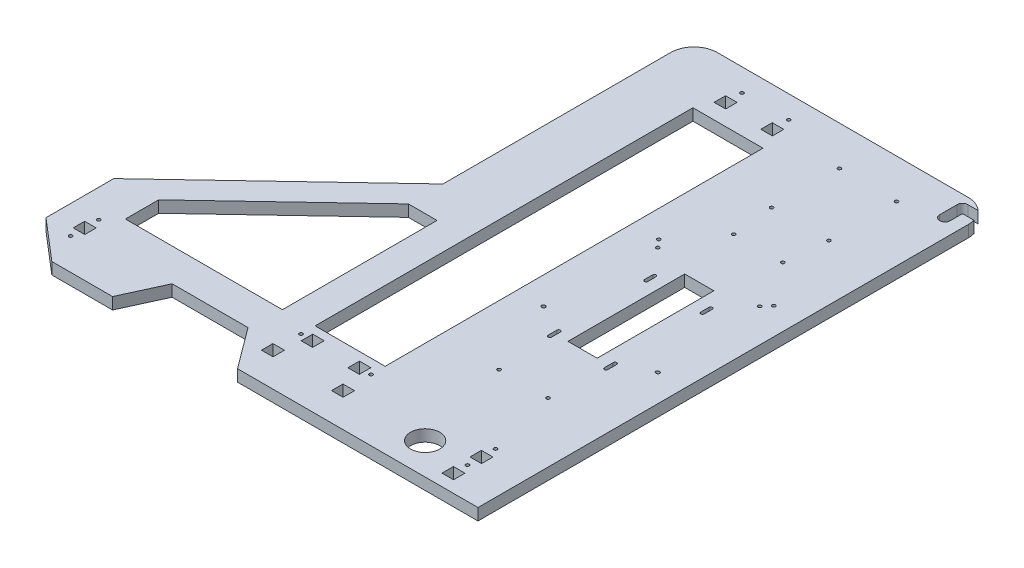
SolidWorks part; units mm, degrees
ref_plane "Front Plane" through (0, 0, 0) normal (0, 0, 1) x (1, 0, 0)
ref_plane "Top Plane" through (0, 0, 0) normal (0, 1, 0) x (1, 0, 0)
ref_plane "Right Plane" through (0, 0, 0) normal (1, 0, 0) x (0, 0, -1)
sketch "Sketch1" plane through (0, 0, 0) normal (0, 1, 0) x (1, 0, 0)
  line L0 (0, 0) -> (-235, 0)
  line L1 (-235, 0) -> (-235, -215)
  line L2 (-235, -215) -> (-380, -352)
  line L3 (-380, -352) -> (-380, -410)
  line L4 (-380, -410) -> (-345, -440)
  line L5 (-345, -440) -> (-293, -440)
  line L6 (-293, -440) -> (-277, -405)
  line L7 (-277, -405) -> (-212, -405)
  line L8 (-212, -405) -> (-185.9255, -440)
  line L9 (-185.9255, -440) -> (0, -440)
  line L10 (0, 0) -> (0, -440)
  line L12 (-293, -440) -> (-185.9255, -440) construction
  dimension "D3" = 235
  dimension "D5" = 58
  dimension "D13" = 190
  dimension "D7" = 35
  dimension "D2" = 126.686
  dimension "D11" = 65
  dimension "D15" = 52
  dimension "D12" = 30
  dimension "D10" = 35
  dimension "D14" = 16
  dimension "D6" = 380
  dimension "D4" = 440
extrude "Boss-Extrude1" add sketch "Sketch1" along normal blind 10
sketch "Sketch16" plane through (0, 10, 0) normal (0, 1, 0) x (1, 0, 0)
  line L0 (0, -440) -> (20, -440)
  line L1 (20, -440) -> (20, 0)
  line L2 (20, 0) -> (0, 0)
  line L3 (0, 0) -> (0, -440)
  dimension "D1" = 20
  dimension "D2" = 90
extrude "Boss-Extrude2" add sketch "Sketch16" against normal through all
sketch "Sketch2" plane through (0, 10, 0) normal (0, 1, 0) x (1, 0, 0)
  line L0 (-235, -215) -> (-235, -405) construction
  line L1 (-277, -405) -> (-212, -405) construction
  line L2 (-345, -440) -> (-345, -318.931) construction
  line L3 (-235, -215) -> (-380, -352) construction
  line L4 (-345, -348.5097) -> (-235, -244.5787)
  line L5 (-235, -244.5787) -> (-210.5, -244.5787)
  line L6 (-210.5, -244.5787) -> (-210.5, -377)
  line L7 (-210.5, -377) -> (-345, -377)
  line L8 (-345, -377) -> (-345, -348.5097)
  line L9 (0, -440) -> (0, 0) construction
  line L10 (-184.5, -375) -> (-124.5, -375)
  line L11 (-184.5, -375) -> (-184.5, -51.4)
  line L12 (-184.5, -51.4) -> (-124.5, -51.4)
  line L13 (-124.5, -375) -> (-124.5, -51.4)
  line L14 (-124.5, -387.1) -> (-184.5, -387.1) construction
  line L15 (-16, -440) -> (-16, 0) construction
  line L16 (20, 0) -> (-235, 0) construction
  line L17 (-355.85, -430.7) -> (-355.85, -329.1824) construction
  line L18 (-20.95, -429.9) -> (-11.05, -429.9)
  line L19 (-20.95, -429.9) -> (-20.95, -420.1)
  line L20 (-20.95, -420.1) -> (-11.05, -420.1)
  line L21 (-11.05, -429.9) -> (-11.05, -420.1)
  line L22 (-20.95, -429.9) -> (-11.05, -420.1) construction
  line L23 (-20.95, -420.1) -> (-11.05, -429.9) construction
  line L24 (-20.95, -405.9) -> (-11.05, -405.9)
  line L25 (-20.95, -405.9) -> (-20.95, -396.1)
  line L26 (-20.95, -396.1) -> (-11.05, -396.1)
  line L27 (-11.05, -405.9) -> (-11.05, -396.1)
  line L28 (-20.95, -405.9) -> (-11.05, -396.1) construction
  line L29 (-20.95, -396.1) -> (-11.05, -405.9) construction
  line L30 (-380, -410) -> (-345, -440) construction
  line L32 (-350.9, -396.1) -> (-360.8, -396.1)
  line L33 (-350.9, -396.1) -> (-350.9, -405.9)
  line L34 (-350.9, -405.9) -> (-360.8, -405.9)
  line L35 (-360.8, -396.1) -> (-360.8, -405.9)
  line L36 (-350.9, -396.1) -> (-360.8, -405.9) construction
  line L37 (-350.9, -405.9) -> (-360.8, -396.1) construction
  line L38 (-185.9255, -440) -> (20, -440) construction
  line L39 (-185.9255, -440) -> (20, -440) construction
  line L40 (-173.774, -33.4) -> (-113.774, -33.4) construction
  line L41 (-154.5, -51.4) -> (-154.5, -33.4) construction
  line L42 (-179.45, -28.5) -> (-169.55, -28.5)
  line L43 (-179.45, -28.5) -> (-179.45, -38.3)
  line L44 (-179.45, -38.3) -> (-169.55, -38.3)
  line L45 (-169.55, -28.5) -> (-169.55, -38.3)
  line L46 (-179.45, -28.5) -> (-169.55, -38.3) construction
  line L47 (-179.45, -38.3) -> (-169.55, -28.5) construction
  line L48 (-129.55, -38.3) -> (-139.45, -28.5) construction
  line L49 (-129.55, -28.5) -> (-139.45, -38.3) construction
  line L50 (-139.45, -28.5) -> (-139.45, -38.3)
  line L51 (-129.55, -38.3) -> (-139.45, -38.3)
  line L52 (-129.55, -28.5) -> (-129.55, -38.3)
  line L53 (-129.55, -28.5) -> (-139.45, -28.5)
  line L54 (-174.5, -33.4) -> (-174.5, -19.4) construction
  line L55 (-134.5, -33.4) -> (-134.5, -19.4) construction
  line L56 (-154.5, -375) -> (-154.5, -440) construction
  line L57 (-174.5, -387.1) -> (-134.5, -387.1) construction
  line L58 (-129.6, -392.05) -> (-139.4, -382.15) construction
  line L59 (-179.4, -382.15) -> (-169.6, -382.15)
  line L60 (-179.4, -382.15) -> (-179.4, -392.05)
  line L61 (-179.4, -392.05) -> (-169.6, -392.05)
  line L62 (-169.6, -382.15) -> (-169.6, -392.05)
  line L63 (-179.4, -382.15) -> (-169.6, -392.05) construction
  line L64 (-179.4, -392.05) -> (-169.6, -382.15) construction
  line L65 (-129.6, -382.15) -> (-139.4, -392.05) construction
  line L66 (-139.4, -382.15) -> (-139.4, -392.05)
  line L67 (-129.6, -392.05) -> (-139.4, -392.05)
  line L68 (-129.6, -382.15) -> (-129.6, -392.05)
  line L69 (-129.6, -382.15) -> (-139.4, -382.15)
  line L70 (-119.55, -416) -> (-129.45, -406.2) construction
  line L71 (-189.45, -406.2) -> (-179.55, -406.2)
  line L72 (-189.45, -406.2) -> (-189.45, -416)
  line L73 (-189.45, -416) -> (-179.55, -416)
  line L74 (-179.55, -406.2) -> (-179.55, -416)
  line L75 (-189.45, -406.2) -> (-179.55, -416) construction
  line L76 (-189.45, -416) -> (-179.55, -406.2) construction
  line L77 (-119.55, -406.2) -> (-129.45, -416) construction
  line L78 (-129.45, -406.2) -> (-129.45, -416)
  line L79 (-119.55, -416) -> (-129.45, -416)
  line L80 (-119.55, -406.2) -> (-119.55, -416)
  line L81 (-119.55, -406.2) -> (-129.45, -406.2)
  line L82 (-360.8, -396.1) -> (-11.05, -396.1) construction
  circle A0 centre (-16, -413) radius 1.45
  circle A1 centre (-16, -389) radius 1.45
  circle A2 centre (-355.85, -413) radius 1.45
  circle A3 centre (-355.85, -389) radius 1.45
  circle A4 centre (-174.5, -19.4) radius 1.45
  circle A5 centre (-134.5, -19.4) radius 1.45
  circle A6 centre (-124.5, -387.1) radius 1.45
  circle A7 centre (-184.5, -387.1) radius 1.45
  point P25 (-16, -425)
  point P30 (-16, -401)
  point P44 (-355.85, -401)
  point P61 (-174.5, -33.4)
  point P72 (-134.5, -33.4)
  point P85 (-174.5, -387.1)
  point P94 (-134.5, -387.1)
  point P95 (-184.5, -411.1)
  point P104 (-124.5, -411.1)
  point P105 (-154.5, -387.1)
  dimension "D13" = 2.9
  dimension "D14" = 2.9
  dimension "D23" = 2.9
  dimension "D24" = 2.9
  dimension "D31" = 2.9
  dimension "D37" = 2.9
  dimension "D1" = 21.5
  dimension "D2" = 28
  dimension "D3" = 24.5
  dimension "D4" = 60
  dimension "D7" = 26
  dimension "D8" = 9.8
  dimension "D9" = 9.9
  dimension "D10" = 9.9
  dimension "D11" = 9.8
  dimension "D12" = 24
  dimension "D15" = 24
  dimension "D19" = 9.9
  dimension "D20" = 9.8
  dimension "D26" = 12
  dimension "D27" = 9.9
  dimension "D28" = 9.8
  dimension "D33" = 9.8
  dimension "D38" = 9.9
  dimension "D39" = 9.8
  dimension "D41" = 24
  dimension "D34" = 30
  dimension "D36" = 12.1
  dimension "D30" = 18
  dimension "D29" = 40
  dimension "D17" = 15
  dimension "D32" = 14
  dimension "D35" = 20
  dimension "D16" = 12
  dimension "D21" = 90
  dimension "D25" = 24
  dimension "D5" = 353.75
  dimension "D22" = 349.75
  dimension "D40" = 30
  dimension "D6" = 65
  dimension "D42" = 0
  dimension "D43" = 0
  dimension "D18" = 16
  dimension "D44" = 9.9
extrude "Cut-Extrude1" cut sketch "Sketch2" against normal through all
fillet "Fillet1" radius 20 2 edges at (-235, 5, 0) (20, 5, 0)
sketch "Sketch11" plane through (0, 10, 0) normal (0, 1, 0) x (1, 0, 0)
  line L0 (-124.5, -213.2) -> (20, -213.2) construction
  line L1 (20, -440) -> (20, -20) construction
  line L3 (-52.25, -213.2) -> (-52.25, -440) construction
  line L6 (-124.5, -375) -> (-124.5, -51.4) construction
  line L8 (-185.9255, -440) -> (20, -440) construction
  circle A0 centre (-52.25, -413) radius 12.5
  circle A1 centre (-16, -413) radius 1.45 construction
  dimension "D1" = 25
  dimension "D2" = 0
  dimension "D3" = 0
extrude "WiringHole" cut sketch "Sketch11" against normal through all
sketch "Sketch9" [suppressed] plane through (0, 10, 0) normal (0, 1, 0) x (1, 0, 0)
  line L0 (-52.25, -400.5) -> (-52.25, 0) construction
  line L1 (0, 0) -> (-215, 0) construction
  line L2 (-124.5, -213.2) -> (20, -213.2) construction
  line L3 (-124.5, -375) -> (-124.5, -51.4) construction
  line L4 (-4.75, -124.7) -> (-4.75, -301.7) construction
  line L6 (-99.75, -124.7) -> (-4.75, -124.7) construction
  line L7 (-4.75, -301.7) -> (-99.75, -301.7) construction
  line L8 (-99.75, -301.7) -> (-99.75, -124.7) construction
  line L9 (20, -440) -> (20, -20) construction
  circle A0 centre (-52.25, -413) radius 12.5 construction
  circle A1 centre (-99.75, -124.7) radius 1.45
  circle A2 centre (-4.75, -124.7) radius 1.45
  circle A3 centre (-4.75, -301.7) radius 1.45
  circle A4 centre (-99.75, -301.7) radius 1.45
  dimension "D3" = 2.9
  dimension "D4" = 2.9
  dimension "D1" = 95
  dimension "D2" = 177
  dimension "D5" = 47.5
extrude "MountingHoles-PSU" [suppressed] cut sketch "Sketch9" against normal through all
sketch "Sketch10" plane through (0, 10, 0) normal (0, 1, 0) x (1, 0, 0)
  line L0 (-124.5, -213.2) -> (20, -213.2) construction
  line L1 (20, -440) -> (20, -20) construction
  line L2 (-64.75, -228.2) -> (-39.75, -228.2) construction
  line L3 (-52.25, -213.2) -> (-52.25, 0) construction
  line L7 (-124.5, -375) -> (-124.5, -51.4) construction
  line L8 (-64.75, -278.2) -> (-39.75, -278.2)
  line L9 (-64.75, -278.2) -> (-64.75, -178.2)
  line L10 (-64.75, -178.2) -> (-39.75, -178.2)
  line L11 (-39.75, -278.2) -> (-39.75, -178.2)
  line L12 (-64.75, -278.2) -> (-39.75, -178.2) construction
  line L13 (-64.75, -178.2) -> (-39.75, -278.2) construction
  line L15 (0, 0) -> (-215, 0) construction
  line L17 (-52.25, -213.2) -> (-52.25, -440) construction
  line L18 (-185.9255, -440) -> (20, -440) construction
  line L19 (-64.75, -213.2) -> (-39.75, -213.2) construction
  line L20 (-52.25, -278.2) -> (-52.25, -178.2) construction
  dimension "D1" = 25
  dimension "D2" = 100
  dimension "D3" = 0
  dimension "D4" = 0
  dimension "D5" = 0
  dimension "D6" = 15
extrude "WiringSlot" cut sketch "Sketch10" against normal through all
sketch "CenterLines" plane through (0, 10, 0) normal (0, 1, 0) x (1, 0, 0)
  line L0 (-52.25, -278.2) -> (-52.25, -178.2) construction
  line L1 (-64.75, -278.2) -> (-39.75, -278.2) construction
  line L2 (-39.75, -178.2) -> (-64.75, -178.2) construction
  line L3 (-64.75, -228.2) -> (-39.75, -228.2) construction
  line L4 (-64.75, -178.2) -> (-64.75, -278.2) construction
  line L5 (-39.75, -278.2) -> (-39.75, -178.2) construction
ref_plane "Plane1" through (-52.25, 0, 0) normal (1, 0, 0) x (0, 0, -1)
sketch "Sketch6" plane through (0, 10, 0) normal (0, 1, 0) x (1, 0, 0)
  line L0 (-52.25, -278.2) -> (-52.25, -178.2) construction
  line L1 (-76.35, -237.05) -> (-28.15, -237.05) construction
  line L2 (-28.15, -192.6) -> (-28.15, -275.1) construction
  line L3 (-64.75, -278.2) -> (-39.75, -278.2) construction
  line L4 (-64.75, -245.9) -> (-39.75, -245.9) construction
  line L5 (-39.75, -178.2) -> (-64.75, -178.2) construction
  line L6 (-28.15, -192.6) -> (-28.15, -199.6) construction
  line L7 (-26.7, -192.6) -> (-26.7, -199.6)
  line L8 (-29.6, -192.6) -> (-29.6, -199.6)
  line L9 (-64.75, -228.2) -> (-39.75, -228.2) construction
  line L10 (-64.75, -178.2) -> (-64.75, -278.2) construction
  line L11 (-39.75, -278.2) -> (-39.75, -178.2) construction
  line L12 (-28.15, -282.1) -> (-28.15, -275.1) construction
  line L13 (-29.6, -282.1) -> (-29.6, -275.1)
  line L14 (-76.35, -274.5) -> (-76.35, -199.6) construction
  line L15 (-28.15, -282.1) -> (-28.15, -199.6) construction
  line L16 (-26.7, -282.1) -> (-26.7, -275.1)
  arc A2 (-26.7, -192.6) -> (-29.6, -192.6) centre (-28.15, -192.6) ccw
  arc A3 (-29.6, -199.6) -> (-26.7, -199.6) centre (-28.15, -199.6) ccw
  circle A4 centre (-76.35, -274.5) radius 1.45
  circle A6 centre (-76.35, -199.6) radius 1.45
  arc A8 (-29.6, -282.1) -> (-26.7, -282.1) centre (-28.15, -282.1) ccw
  arc A9 (-26.7, -275.1) -> (-29.6, -275.1) centre (-28.15, -275.1) ccw
  point P20 (-28.15, -196.1)
  point P25 (-28.15, -278.6)
  dimension "D8" = 2.9
  dimension "D12" = 2.9
  dimension "D4" = 1.45
  dimension "D5" = 1.45
  dimension "D11" = 82.5
  dimension "D14" = 74.9
  dimension "D2" = 24.1
  dimension "D3" = 48.2
  dimension "D6" = 8.85
  dimension "D9" = 7
  dimension "D10" = 7
extrude "MountingHoles-RAMPS" cut sketch "Sketch6" against normal through all
mirror "Mirror1" about plane through (-52.25, 0, 0) normal (1, 0, 0) of "MountingHoles-RAMPS"
sketch "Sketch5" plane through (0, 10, 0) normal (0, 1, 0) x (1, 0, 0)
  line L0 (-39.75, -228.2) -> (-64.75, -228.2) construction
  line L3 (-39.75, -278.2) -> (-39.75, -178.2) construction
  line L5 (-64.75, -178.2) -> (-64.75, -278.2) construction
  line L7 (-31.25, -127.7) -> (-73.25, -127.7) construction
  line L8 (-31.25, -328.7) -> (-73.25, -328.7) construction
  line L9 (-52.25, -228.2) -> (-52.25, -127.7) construction
  line L10 (-52.25, -228.2) -> (-52.25, -328.7) construction
  circle A0 centre (-73.25, -127.7) radius 1.45
  circle A1 centre (-31.25, -127.7) radius 1.45
  circle A2 centre (-31.25, -328.7) radius 1.45
  circle A3 centre (-73.25, -328.7) radius 1.45
  point P17 (-52.25, -127.7)
  point P22 (-52.25, -328.7)
  dimension "D2" = 2.9
  dimension "D5" = 2.9
  dimension "D6" = 2.9
  dimension "D7" = 2.9
  dimension "D3" = 201
  dimension "D4" = 100.5
  dimension "D8" = 21
  dimension "D9" = 21
  dimension "D10" = 100.5
extrude "MountingHoles-Melzi" cut sketch "Sketch5" against normal through all
sketch "Sketch13" plane through (0, 0, 0) normal (0, -1, 0) x (-1, 0, 0)
  line L0 (64.75, -213.2) -> (124.5, -213.2) construction
  line L1 (124.5, -375) -> (124.5, -51.4) construction
  line L2 (101.46, -262.715) -> (101.46, -163.685) construction
  line L3 (52.25, -278.2) -> (52.25, -178.2) construction
  line L4 (64.75, -178.2) -> (64.75, -278.2) construction
  line L6 (101.46, -262.715) -> (3.56, -262.715) construction
  circle A0 centre (101.46, -163.685) radius 1.45
  circle A1 centre (101.46, -262.715) radius 1.45
  circle A2 centre (8.62, -170.165) radius 1.45
  circle A3 centre (3.56, -262.715) radius 1.45
  point P11 (101.46, -213.2)
  dimension "D8" = 2.9
  dimension "D6" = 2.9
  dimension "D1" = 2.9
  dimension "D2" = 49.515
  dimension "D3" = 49.21
  dimension "D4" = 6.48
  dimension "D5" = 92.84
  dimension "D7" = 97.9
extrude "Mountingholes-Smoothieboard" cut sketch "Sketch13" against normal through all
mirror "Flipped" about plane through (-52.25, 0, 0) normal (1, 0, 0) of "Mountingholes-Smoothieboard"
sketch "Sketch21" plane through (0, 10, 0) normal (0, 1, 0) x (1, 0, 0)
  line L0 (-52.25, -178.2) -> (-52.25, 0) construction
  line L1 (-39.75, -178.2) -> (-64.75, -178.2) construction
  line L2 (0, 0) -> (-215, 0) construction
  line L3 (-52.25, -62.7) -> (-23.3697, -62.7) construction
  circle A0 centre (-27.75, -33.7) radius 1.45
  circle A1 centre (-76.75, -33.7) radius 1.45
  circle A2 centre (-76.75, -91.7) radius 1.45
  circle A3 centre (-27.75, -91.7) radius 1.45
  circle A4 centre (-31.25, -127.7) radius 1.45 construction
  dimension "D1" = 2.9
  dimension "D2" = 24.5
  dimension "D3" = 29
  dimension "D4" = 65
extrude "Pi" cut sketch "Sketch21" against normal through all
sketch "Sketch17" plane through (0, 10, 0) normal (0, 1, 0) x (1, 0, 0)
  line L0 (0, 0) -> (20, 0) construction
  line L1 (20, -23.6361) -> (20, 0) construction
  line L2 (20, -440) -> (20, -20) construction
  line L3 (20, -10) -> (5, -10) construction
  line L4 (20, -14.5) -> (5, -14.5)
  line L5 (20, -5.5) -> (5, -5.5)
  arc A0 (20, -14.5) -> (20, -5.5) centre (20, -10) ccw
  arc A1 (5, -5.5) -> (5, -14.5) centre (5, -10) ccw
  point P8 (12.5, -10)
  dimension "D1" = 9
  dimension "D2" = 15
  dimension "D3" = 10
extrude "Cut-Extrude3" cut sketch "Sketch17" against normal through all
sketch "Sketch18" plane through (0, 10, 0) normal (0, 1, 0) x (1, 0, 0)
  line L0 (5, -5.5) -> (5, -14.5) construction
  line L1 (0.5, -10) -> (5, -10) construction
  line L2 (5, -10) -> (5, -25) construction
  line L3 (9.5, -10) -> (9.5, -25)
  line L4 (0.5, -10) -> (0.5, -25)
  arc A0 (5, -5.5) -> (5, -14.5) centre (5, -10) ccw construction
  arc A1 (9.5, -10) -> (0.5, -10) centre (5, -10) ccw
  arc A2 (0.5, -25) -> (9.5, -25) centre (5, -25) ccw
  point P10 (5, -17.5)
  dimension "D1" = 9
  dimension "D2" = 0
  dimension "D3" = 15
extrude "Cut-Extrude4" cut sketch "Sketch18" against normal through all
sketch "Sketch19" plane through (0, 10, 0) normal (0, 1, 0) x (1, 0, 0)
  line L0 (-5, -25) -> (15, -25) construction
  line L1 (5, -25) -> (5, -5.5) construction
  circle A0 centre (15, -25) radius 1.45
  arc A1 (5, -5.5) -> (0.5, -10) centre (5, -10) ccw construction
  circle A2 centre (-5, -25) radius 1.45
  dimension "D2" = 2.9
extrude "Cut-Extrude5" [suppressed] cut sketch "Sketch19" against normal through all
equation "\"Y-ROD-SPACING\"=75"
equation "\"Y-BED-OFFSET\"=2"
equation "\"Y-BED-ROD-INSET\"=3.5"
equation "\"T-SLOT-NUT-FILLET-RADIUS\"=0.5"
equation "\"T-SLOT-SCREW-SHAFT-RADIUS\"=1.55"
equation "\"T-SLOT-SCREW-SHAFT-CUTOUT-LENGTH\"=11.0"
equation "\"T-SLOT-NUT-DEPTH\"=3.5"
equation "\"T-SLOT-NUT-WIDTH\"=2.85"
equation "\"T-SLOT-NUT-END-DISTANCE\"=8"
equation "\"ACRYLIC-TAB-CUTOUT-SIZE\"=\"ACRYLIC-THICKNESS\"+\"ACRYLIC-TAB-TOLERANCE\"*2"
equation "\"ACRYLIC-TAB-WIDTH\"=\"ACRYLIC-THICKNESS\""
equation "\"ACRYLIC-M3-HOLE\"=2.9"
equation "\"SMOOTHROD-CAP-SCREW-DISTANCE\"=20"
equation "\"FRAME-WIDTH-INNER\"=370"
equation "\"D24@Sketch2\"=\"ACRYLIC-M3-HOLE\""
equation "\"D23@Sketch2\"=\"ACRYLIC-M3-HOLE\""
equation "\"D19@Sketch2\"=\"ACRYLIC-THICKNESS\"-\"KERF\"*2"
equation "\"D20@Sketch2\"=\"ACRYLIC-TAB-WIDTH\"-\"KERF\"*4"
equation "\"D37@Sketch2\"=\"ACRYLIC-M3-HOLE\""
equation "\"D33@Sketch2\"=\"ACRYLIC-TAB-WIDTH\"-\"KERF\"*4"
equation "\"D38@Sketch2\"=\"ACRYLIC-THICKNESS\"-\"KERF\"*2"
equation "\"D39@Sketch2\"=\"ACRYLIC-TAB-WIDTH\"-\"KERF\"*4"
equation "\"D13@Sketch2\"=\"ACRYLIC-M3-HOLE\""
equation "\"D14@Sketch2\"=\"ACRYLIC-M3-HOLE\""
equation "\"D8@Sketch2\"=\"ACRYLIC-TAB-WIDTH\"-\"KERF\"*4"
equation "\"D9@Sketch2\"=\"ACRYLIC-THICKNESS\"-\"KERF\"*2"
equation "\"D10@Sketch2\"=\"ACRYLIC-THICKNESS\"-\"KERF\"*2"
equation "\"D11@Sketch2\"=\"ACRYLIC-TAB-WIDTH\"-\"KERF\"*4"
equation "\"D31@Sketch2\"=\"ACRYLIC-M3-HOLE\""
equation "\"D27@Sketch2\"=\"ACRYLIC-THICKNESS\"-\"KERF\"*2"
equation "\"D28@Sketch2\"=\"ACRYLIC-TAB-WIDTH\"-\"KERF\"*4"
equation "\"NEMA17-HOLE-SPACING\"=31"
equation "\"NEMA17-CENTRAL-CUTOUT\"=22.5"
equation "\"Z-BRACKET-REACH\"=55"
equation "\"TOP-BRACKET-SPACING\"=40"
equation "\"D29@Sketch2\"=\"TOP-BRACKET-SPACING\""
equation "\"ACRYLIC-THICKNESS\"=10"
equation "\"SMOOTHROD-Z-LENGTH\"=350"
equation "\"D5@Sketch2\"=\"SMOOTHROD-Z-LENGTH\"-\"SMOOTHROD-TIGHTENING-HEADROOM\"+4"
equation "\"SMOOTHROD-X-LENGTH\"=350"
equation "\"SMOOTHROD-Y-LENGTH\"=350"
equation "\"D22@Sketch2\"=\"SMOOTHROD-Y-LENGTH\"-\"SMOOTHROD-TIGHTENING-HEADROOM\""
equation "\"SMOOTHROD-TIGHTENING-HEADROOM\"=.25"
equation "\"X-ROD-SPACING\"=45"
equation "\"Z-ROD-SPACING\"=17.5"
equation "\"LEADSCREW-Z-LENGTH\"=300"
equation "\"SCREW-HEAD-RADIUS\"=6"
equation "\"PRINTED-X-SMOOTHROD-DIAMETER\"=8.4"
equation "\"PRINTED-X-SMOOTHROD-CUTOUT\"=10"
equation "\"PRINTED-X-BASE-HEIGHT\"=10"
equation "\"PRINTED-LM8UU-CUTOUT-SIZE\"=15.5"
equation "\"PRINTED-LM8UU-CUTOUT-LENGTH\"=24.5"
equation "\"PRINTED-X-IDLER-HEIGHT\"=16"
equation "\"PSU-MOUNTING-WIDTH\"=95"
equation "\"PSU-MOUNTING-HEIGHT\"=177"
equation "\"D1@Sketch9\"=\"PSU-MOUNTING-WIDTH\""
equation "\"D3@Sketch9\"=\"ACRYLIC-M3-HOLE\""
equation "\"D1@Boss-Extrude1\"=\"ACRYLIC-THICKNESS\""
equation "\"D6@Sketch1\"=\"SMOOTHROD-Y-LENGTH\"+30"
equation "\"D4@Sketch9\"=\"ACRYLIC-M3-HOLE\""
equation "\"D2@Sketch9\"=\"PSU-MOUNTING-HEIGHT\""
equation "\"D5@Sketch9\"=\"PSU-MOUNTING-WIDTH\"/2"
equation "\"D4@Sketch1\"=\"SMOOTHROD-Z-LENGTH\"+90"
equation "\"D8@Sketch6\"=\"ACRYLIC-M3-HOLE\""
equation "\"D12@Sketch6\"=\"ACRYLIC-M3-HOLE\""
equation "\"D2@Sketch5\"=\"ACRYLIC-M3-HOLE\""
equation "\"D5@Sketch5\"=\"ACRYLIC-M3-HOLE\""
equation "\"D6@Sketch5\"=\"ACRYLIC-M3-HOLE\""
equation "\"D7@Sketch5\"=\"ACRYLIC-M3-HOLE\""
equation "\"D1@Sketch13\"=\"ACRYLIC-M3-HOLE\""
equation "\"D6@Sketch13\"=\"ACRYLIC-M3-HOLE\""
equation "\"D8@Sketch13\"=\"ACRYLIC-M3-HOLE\""
equation "\"D4@Sketch6\"=\"ACRYLIC-M3-HOLE\"/2"
equation "\"D5@Sketch6\"=\"ACRYLIC-M3-HOLE\"/2"
equation "\"Y-BED-SCREW-SPACING\"=209"
equation "\"Y-BED-SCREW-CUTOUT-SLOT-HEIGHT\"=2"
equation "\"ACRYLIC-THICKNESS2\"=4.5"
equation "\"ACRYLIC-TAB-TOLERANCE\"=-.05"
equation "\"Z-ROD-INSET\"=16"
equation "\"SCREW-LENGTH-FRAME\"=\"ACRYLIC-THICKNESS\" + 10"
equation "\"SCREW-LENGTH-MOTOR\"=\"ACRYLIC-THICKNESS\" + 5"
equation "\"SCREW-LENGTH-EXTRUDER\"=28"
equation "\"Y-BELT-TO-ROD-DISTANCE\"=20"
equation "\"SPOOL-HOLDER-ROD-SPACING\"=150"
equation "\"ACRYLIC-X-CARRIAGE-WIDTH\"=55"
equation "\"ACRYLIC-X-CARRIAGE-HEIGHT\"=75"
equation "\"ACRYLIC-X-CARRIAGE-LM8UU-CUTOUT-WIDTH\"=24.25"
equation "\"ACRYLIC-X-CARRIAGE-SCREW-SPACING-X\"=15"
equation "\"ACRYLIC-X-CARRIAGE-SCREW-SPACING-Y\"=33"
equation "\"ACRYLIC-X-CARRIAGE-CENTER-TAB-SPACING\"=14"
equation "\"ACRYLIC-X-CARRIAGE-EXTRUDER-OFFSET\"=26"
equation "\"ACRYLIC-X-CARRIAGE-EXTRUDER-ANGLE\"=90"
equation "\"ACRYLIC-X-CARRIAGE-EXTRUDER-SHELF-DEPTH\"=\"ACRYLIC-X-CARRIAGE-EXTRUDER-OFFSET\" + 28"
equation "\"ACRYLIC-X-CARRIAGE-EXTRUDER-BRACE-SPACING\"=23"
equation "\"ACRYLIC-X-CARRIAGE-EXTRUDER-BRACE-TAB-OFFSET\"=20"
equation "\"ACRYLIC-X-CARRIAGE-EXTRUDER-BRACE-HEIGHT\"=35"
equation "\"ACRYLIC-X-CARRIAGE-EXTRUDER-BRACE-SCREW-SPACING\"=22"
equation "\"D1@Sketch19\"=\"SMOOTHROD-CAP-SCREW-DISTANCE\"/2"
equation "\"D2@Sketch19\"=\"ACRYLIC-M3-HOLE\""
equation "\"D1@Sketch21\"=\"ACRYLIC-M3-HOLE\""
equation "\"KERF\"=0.05"
equation "\"PRINTED-M3-HOLE\"=3.5"
equation "\"PRINTED-M3-NUT-AF\"=6.25"
equation "\"ACRYLIC-X-CARRIAGE-LM8UU-CUTOUT-HEIGHT\"=11.0"
equation "\"ACRYLIC-X-CARRIAGE-DUAL-WIDTH-MULTIPLIER\"=1.65"
equation "\"ACRYLIC-X-CARRIAGE-DUAL-HOTEND-SPACING\"=42"
equation "\"ACRYLIC-X-CARRIAGE-DUAL-WIDTH\"=75"
equation "\"ACRYLIC-X-CARRIAGE-DUAL-FAN-OFFSET\"=52"
equation "\"ACRYLIC-X-CARRIAGE-DUAL-FAN-HEIGHT\"=20"
equation "\"ACRYLIC-X-CARRIAGE-DUAL-HOTEND-SEPARATION\"=36"
equation "\"ACRYLIC-X-CARRIAGE-DUAL-MOUNT-PLATE-DEPTH\"=75"
equation "\"ACRYLIC-X-CARRIAGE-DUAL-MOUNT-BRACE-WIDTH\"=33"
equation "\"ACRYLIC-X-CARRIAGE-DUAL-MOUNT-SCREW-WIDTH\"=40"
equation "\"BLOWER-FAN-WIDTH\"=15"
equation "\"D44@Sketch2\"=\"ACRYLIC-THICKNESS\"-\"KERF\"*2"
